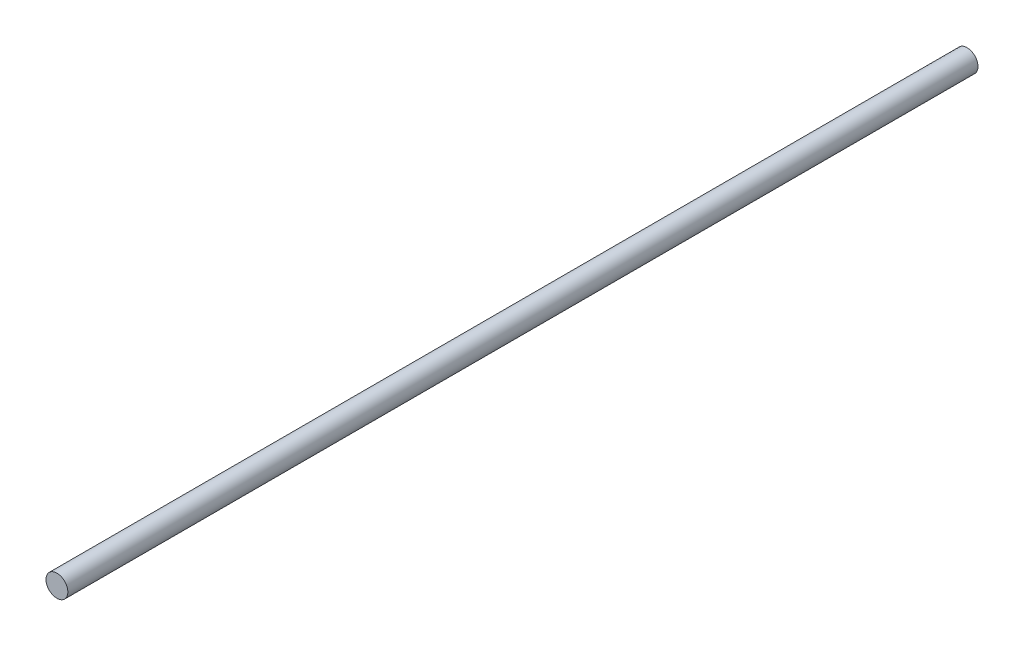
SolidWorks part; units mm, degrees
ref_plane "Front Plane" through (0, 0, 0) normal (0, 0, 1) x (1, 0, 0)
ref_plane "Top Plane" through (0, 0, 0) normal (0, 1, 0) x (1, 0, 0)
ref_plane "Right Plane" through (0, 0, 0) normal (1, 0, 0) x (0, 0, -1)
ref_axis "Axis1" through (0, 0, -7.5) along (0, 0, 1)
sketch "Sketch1" plane through (0, 0, 0) normal (0, 0, 1) x (1, 0, 0)
  circle A0 centre (0, 0) radius 3
  dimension "D1" = 6
extrude "Main" add sketch "Sketch1" along normal blind 250
